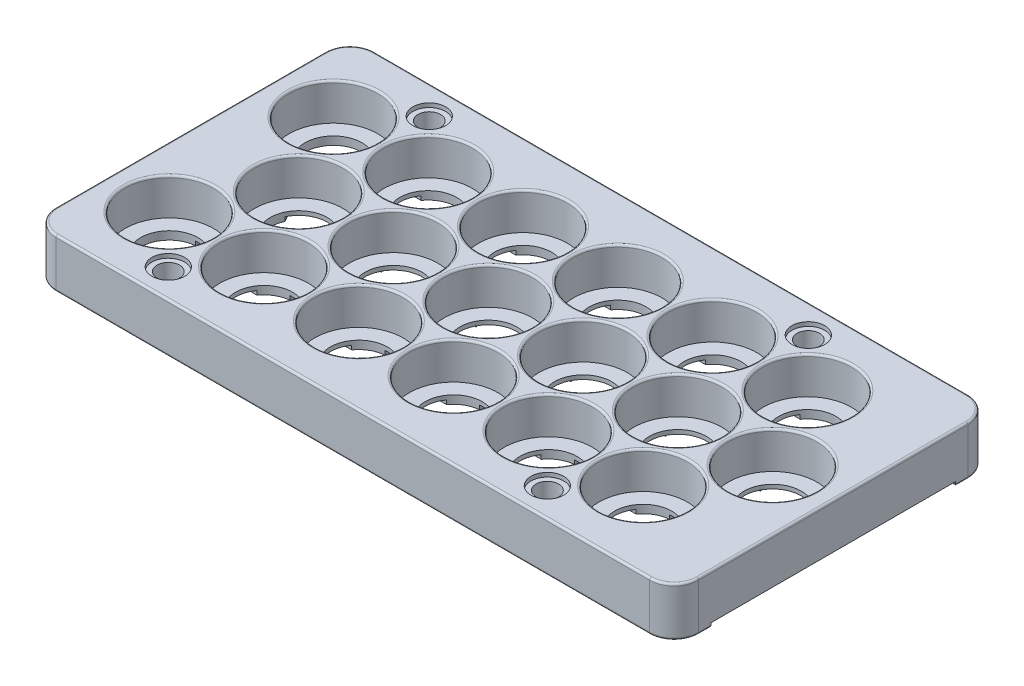
SolidWorks part; units mm, degrees
ref_plane "Front Plane" through (0, 0, 0) normal (0, 0, 1) x (1, 0, 0)
ref_plane "Top Plane" through (0, 0, 0) normal (0, 1, 0) x (1, 0, 0)
ref_plane "Right Plane" through (0, 0, 0) normal (1, 0, 0) x (0, 0, -1)
sketch "Sketch1" plane through (0, 0, 0) normal (0, 1, 0) x (1, 0, 0)
  line L0 (0, 0) -> (11.575, -20.0485) construction
  line L1 (11.575, -20.0485) -> (0, -40.097) construction
  line L2 (0, 0) -> (11.575, 0) construction
  line L3 (11.575, 0) -> (11.575, -20.0485) construction
  line L4 (11.575, -20.0485) -> (11.575, -40.097) construction
  line L5 (11.575, -40.097) -> (0, -40.097) construction
  line L6 (0, 0) -> (23.15, 0) construction
  line L7 (0, 0) -> (23.15, 0) construction
  line L8 (-14.825, -58.922) -> (142.15, -58.922)
  line L9 (-14.825, -58.922) -> (-14.825, 18.825)
  line L10 (-14.825, 18.825) -> (142.15, 18.825)
  line L11 (142.15, -58.922) -> (142.15, 18.825)
  circle A0 centre (0, 0) radius 10.825
  circle A1 centre (11.575, -20.0485) radius 10.825
  circle A2 centre (0, -40.097) radius 10.825
  circle A3 centre (23.15, 0) radius 10.825
  circle A4 centre (34.725, -20.0485) radius 10.825
  circle A5 centre (23.15, -40.097) radius 10.825
  circle A6 centre (46.3, 0) radius 10.825
  circle A7 centre (57.875, -20.0485) radius 10.825
  circle A8 centre (46.3, -40.097) radius 10.825
  circle A9 centre (69.45, 0) radius 10.825
  circle A10 centre (81.025, -20.0485) radius 10.825
  circle A11 centre (69.45, -40.097) radius 10.825
  circle A12 centre (92.6, 0) radius 10.825
  circle A13 centre (104.175, -20.0485) radius 10.825
  circle A14 centre (92.6, -40.097) radius 10.825
  circle A15 centre (115.75, 0) radius 10.825
  circle A16 centre (127.325, -20.0485) radius 10.825
  circle A17 centre (115.75, -40.097) radius 10.825
  circle A18 centre (0, 0) radius 7
  circle A19 centre (11.575, -20.0485) radius 7
  circle A20 centre (0, -40.097) radius 7
  circle A21 centre (23.15, 0) radius 7
  circle A22 centre (34.725, -20.0485) radius 7
  circle A23 centre (23.15, -40.097) radius 7
  circle A24 centre (46.3, 0) radius 7
  circle A25 centre (57.875, -20.0485) radius 7
  circle A26 centre (46.3, -40.097) radius 7
  circle A27 centre (69.45, 0) radius 7
  circle A28 centre (81.025, -20.0485) radius 7
  circle A29 centre (69.45, -40.097) radius 7
  circle A30 centre (92.6, 0) radius 7
  circle A31 centre (104.175, -20.0485) radius 7
  circle A32 centre (92.6, -40.097) radius 7
  circle A33 centre (115.75, 0) radius 7
  circle A34 centre (127.325, -20.0485) radius 7
  circle A35 centre (115.75, -40.097) radius 7
  dimension "D3" = 21.65
  dimension "D11" = 14
  dimension "D1" = 60
  dimension "D2" = 60
  dimension "D4" = 1.5
  dimension "D6" = 23.15
  dimension "D7" = 4
  dimension "D8" = 4
  dimension "D9" = 8
  dimension "D10" = 8
  dimension "D13" = 23.15
  dimension "D12" = 6
extrude "Boss-Extrude2" add sketch "Sketch1" along normal blind 11 contours L8 L11 L10 L9 A17 A16 A15 A14 A13 A12 A11 A10 A9 A8 A7 A6 A5 A4 A3 A2 A1 A0 region at (-13.0733, 0, 20.0485)
extrude "Boss-Extrude3" add sketch "Sketch1<3>" along normal blind 2 contours A0 A18 | A3 A21 | A6 A24 | A9 A27 | A12 A30 | A15 A33 | A1 A19 | A4 A22 | A7 A25 | A10 A28 | A13 A31 | A16 A34 | A17 A35 | A14 A32 | A11 A29 | A8 A26 | A5 A23 | A2 A20 region at (-10.5188, 0, 0) region at (1.0562, 0, 20.0485) region at (-10.5188, 0, 40.097) region at (12.6312, 0, 0) region at (24.2062, 0, 20.0485) region at (12.6312, 0, 40.097) region at (35.7812, 0, 0) region at (47.3562, 0, 20.0485) region at (35.7812, 0, 40.097) region at (58.9312, 0, 0) region at (70.5062, 0, 20.0485) region at (58.9312, 0, 40.097) region at (82.0812, 0, 0) region at (93.6562, 0, 20.0485) region at (82.0812, 0, 40.097) region at (105.2312, 0, 0) region at (116.8062, 0, 20.0485) region at (105.2312, 0, 40.097)
sketch "Sketch1<3>" plane through (0, 0, 0) normal (0, 1, 0) x (1, 0, 0) same geometry as "Sketch1"
sketch "Sketch2" plane through (0, 0, 0) normal (0, -1, 0) x (1, 0, 0)
  line L0 (0, 40.097) -> (11.575, 20.0485) construction
  line L1 (3.4641, 42.097) -> (15.0391, 22.0485)
  line L2 (-3.4641, 38.097) -> (8.1109, 18.0485)
  line L3 (11.575, 20.0485) -> (0, 0) construction
  line L4 (15.0391, 18.0485) -> (3.4641, -2)
  line L5 (8.1109, 22.0485) -> (-3.4641, 2)
  line L6 (19.6859, 38.097) -> (31.2609, 18.0485)
  line L7 (26.6141, 42.097) -> (38.1891, 22.0485)
  line L8 (31.2609, 22.0485) -> (19.6859, 2)
  line L9 (38.1891, 18.0485) -> (26.6141, -2)
  line L10 (23.15, 40.097) -> (34.725, 20.0485) construction
  line L11 (34.725, 20.0485) -> (23.15, 0) construction
  line L12 (42.8359, 38.097) -> (54.4109, 18.0485)
  line L13 (49.7641, 42.097) -> (61.3391, 22.0485)
  line L14 (54.4109, 22.0485) -> (42.8359, 2)
  line L15 (61.3391, 18.0485) -> (49.7641, -2)
  line L16 (46.3, 40.097) -> (57.875, 20.0485) construction
  line L17 (57.875, 20.0485) -> (46.3, 0) construction
  line L18 (65.9859, 38.097) -> (77.5609, 18.0485)
  line L19 (72.9141, 42.097) -> (84.4891, 22.0485)
  line L20 (77.5609, 22.0485) -> (65.9859, 2)
  line L21 (84.4891, 18.0485) -> (72.9141, -2)
  line L22 (69.45, 40.097) -> (81.025, 20.0485) construction
  line L23 (81.025, 20.0485) -> (69.45, 0) construction
  line L24 (89.1359, 38.097) -> (100.7109, 18.0485)
  line L25 (96.0641, 42.097) -> (107.6391, 22.0485)
  line L26 (100.7109, 22.0485) -> (89.1359, 2)
  line L27 (107.6391, 18.0485) -> (96.0641, -2)
  line L28 (92.6, 40.097) -> (104.175, 20.0485) construction
  line L29 (104.175, 20.0485) -> (92.6, 0) construction
  line L30 (112.2859, 38.097) -> (123.8609, 18.0485)
  line L31 (119.2141, 42.097) -> (130.7891, 22.0485)
  line L32 (123.8609, 22.0485) -> (112.2859, 2)
  line L33 (130.7891, 18.0485) -> (119.2141, -2)
  line L34 (115.75, 40.097) -> (127.325, 20.0485) construction
  line L35 (127.325, 20.0485) -> (115.75, 0) construction
  line L36 (-3.4641, 38.097) -> (19.6859, 38.097) construction
  line L37 (0, 40.097) -> (115.75, 40.097) construction
  line L38 (0, 44.097) -> (115.75, 44.097)
  line L39 (0, 36.097) -> (115.75, 36.097)
  line L40 (11.575, 20.0485) -> (127.325, 20.0485) construction
  line L41 (11.575, 24.0485) -> (127.325, 24.0485)
  line L42 (11.575, 16.0485) -> (127.325, 16.0485)
  line L43 (0, 0) -> (115.75, 0) construction
  line L44 (0, 4) -> (115.75, 4)
  line L45 (0, -4) -> (115.75, -4)
  arc A0 (3.4641, 42.097) -> (-3.4641, 38.097) centre (0, 40.097) ccw
  arc A1 (8.1109, 18.0485) -> (15.0391, 22.0485) centre (11.575, 20.0485) ccw
  arc A2 (15.0391, 18.0485) -> (8.1109, 22.0485) centre (11.575, 20.0485) ccw
  arc A3 (-3.4641, 2) -> (3.4641, -2) centre (0, 0) ccw
  arc A4 (26.6141, 42.097) -> (19.6859, 38.097) centre (23.15, 40.097) ccw
  arc A5 (31.2609, 18.0485) -> (38.1891, 22.0485) centre (34.725, 20.0485) ccw
  arc A6 (38.1891, 18.0485) -> (31.2609, 22.0485) centre (34.725, 20.0485) ccw
  arc A7 (19.6859, 2) -> (26.6141, -2) centre (23.15, 0) ccw
  arc A8 (49.7641, 42.097) -> (42.8359, 38.097) centre (46.3, 40.097) ccw
  arc A9 (54.4109, 18.0485) -> (61.3391, 22.0485) centre (57.875, 20.0485) ccw
  arc A10 (61.3391, 18.0485) -> (54.4109, 22.0485) centre (57.875, 20.0485) ccw
  arc A11 (42.8359, 2) -> (49.7641, -2) centre (46.3, 0) ccw
  arc A12 (72.9141, 42.097) -> (65.9859, 38.097) centre (69.45, 40.097) ccw
  arc A13 (77.5609, 18.0485) -> (84.4891, 22.0485) centre (81.025, 20.0485) ccw
  arc A14 (84.4891, 18.0485) -> (77.5609, 22.0485) centre (81.025, 20.0485) ccw
  arc A15 (65.9859, 2) -> (72.9141, -2) centre (69.45, 0) ccw
  arc A16 (96.0641, 42.097) -> (89.1359, 38.097) centre (92.6, 40.097) ccw
  arc A17 (100.7109, 18.0485) -> (107.6391, 22.0485) centre (104.175, 20.0485) ccw
  arc A18 (107.6391, 18.0485) -> (100.7109, 22.0485) centre (104.175, 20.0485) ccw
  arc A19 (89.1359, 2) -> (96.0641, -2) centre (92.6, 0) ccw
  arc A20 (119.2141, 42.097) -> (112.2859, 38.097) centre (115.75, 40.097) ccw
  arc A21 (123.8609, 18.0485) -> (130.7891, 22.0485) centre (127.325, 20.0485) ccw
  arc A22 (130.7891, 18.0485) -> (123.8609, 22.0485) centre (127.325, 20.0485) ccw
  arc A23 (112.2859, 2) -> (119.2141, -2) centre (115.75, 0) ccw
  arc A24 (0, 44.097) -> (0, 36.097) centre (0, 40.097) ccw
  arc A25 (115.75, 36.097) -> (115.75, 44.097) centre (115.75, 40.097) ccw
  arc A26 (11.575, 24.0485) -> (11.575, 16.0485) centre (11.575, 20.0485) ccw
  arc A27 (127.325, 16.0485) -> (127.325, 24.0485) centre (127.325, 20.0485) ccw
  arc A28 (0, 4) -> (0, -4) centre (0, 0) ccw
  arc A29 (115.75, -4) -> (115.75, 4) centre (115.75, 0) ccw
  point P3 (5.7875, 30.0727)
  point P8 (5.7875, 10.0242)
  point P18 (28.9375, 30.0727)
  point P25 (28.9375, 10.0242)
  point P34 (52.0875, 30.0727)
  point P39 (52.0875, 10.0242)
  point P48 (75.2375, 30.0727)
  point P53 (75.2375, 10.0242)
  point P62 (98.3875, 30.0727)
  point P67 (98.3875, 10.0242)
  point P76 (121.5375, 30.0727)
  point P81 (121.5375, 10.0242)
  point P91 (57.875, 40.097)
  point P96 (69.45, 20.0485)
  point P103 (57.875, 0)
  circle M62 centre (0, 0) radius 7
  circle M63 centre (23.15, 0) radius 7
  circle M64 centre (46.3, 0) radius 7
  circle M65 centre (69.45, 0) radius 7
  circle M66 centre (92.6, 0) radius 7
  circle M67 centre (115.75, 0) radius 7
  circle M68 centre (11.575, 20.0485) radius 7
  circle M69 centre (34.725, 20.0485) radius 7
  circle M70 centre (57.875, 20.0485) radius 7
  circle M71 centre (81.025, 20.0485) radius 7
  circle M72 centre (104.175, 20.0485) radius 7
  circle M73 centre (127.325, 20.0485) radius 7
  circle M74 centre (115.75, 40.097) radius 7
  circle M75 centre (92.6, 40.097) radius 7
  circle M76 centre (69.45, 40.097) radius 7
  circle M77 centre (46.3, 40.097) radius 7
  circle M78 centre (23.15, 40.097) radius 7
  circle M79 centre (0, 40.097) radius 7
  dimension "D1" = 8
  dimension "D3" = 23.15
  dimension "D4" = 8
  dimension "D5" = 8
  dimension "D6" = 8
extrude "Cut-Extrude1" cut sketch "Sketch2" against normal blind 1 contours L1 L39 L38 M78 M79 | L7 L39 L38 M77 M78 | L39 L2 L1 M79 M68 | L42 L8 L6 L41 M68 M69 | L6 L41 L7 L39 M69 M78 | L12 L41 L13 L39 M70 M77 | L13 L39 L38 M76 M77 | L18 L41 L19 L39 M71 M76 | L19 L39 L38 M75 M76 | L24 L41 L25 L39 M72 M75 | L25 L39 L38 M74 M75 | L30 L41 L31 M73 M74 | L42 L32 L30 L41 M72 M73 | L42 L26 L24 L41 M71 M72 | L42 L20 L18 L41 M70 M71 | L42 L14 L12 L41 M69 M70 | L45 L44 L4 M62 M63 | L44 L4 L5 M62 M68 | L45 L44 L9 M63 M64 | L45 L44 L15 M64 M65 | L45 L44 L21 M65 M66 | L45 L44 L27 M66 M67 | L44 L27 L42 L26 M66 M72 | L42 L32 L33 M67 M73 | L44 L21 L42 L20 M65 M71 | L44 L15 L42 L14 M64 M70 | L39 L13 M77 | L39 L25 M75 | L39 L19 M76 | L41 L6 M69 | L44 L4 M62 | L44 L15 M64 | L44 L21 M65 | L44 L27 M66 | L41 L30 M73 | L32 L42 M73 | L41 L24 M72 | L26 L42 M72 | L41 L18 M71 | L20 L42 M71 | L41 L12 M70 | L14 L42 M70 | L44 L9 L42 L8 M63 M69 | L8 L42 M69 | L39 L7 M78 | L39 L1 M79 | L44 A29 L45 A28 region at (11.6138, 0, 40.1242) region at (6.3461, 0, 36.4331) region at (5.7834, 0, 30.0255) region at (23.0718, 0, 20.0485) region at (28.9375, 0, 30.0727) region at (34.7638, 0, 40.1242) region at (28.3789, 0, 23.7124) region at (5.7834, 0, 10.0715) region at (29.4961, 0, 36.4331) region at (57.9138, 0, 40.1242) region at (28.3789, 0, 16.3846) region at (28.9375, 0, 10.0242) region at (6.3461, 0, 3.6639) region at (11.6138, 0, -0.0272) region at (52.0875, 0, 30.0727) region at (46.2218, 0, 20.0485) region at (52.6461, 0, 36.4331) region at (81.0638, 0, 40.1242) region at (51.5289, 0, 23.7124) region at (34.7638, 0, -0.0272) region at (75.2375, 0, 30.0727) region at (75.7961, 0, 36.4331) region at (104.2138, 0, 40.1242) region at (74.6789, 0, 23.7124) region at (69.3718, 0, 20.0485) region at (51.5289, 0, 16.3846) region at (52.0875, 0, 10.0242) region at (57.9138, 0, -0.0272) region at (98.3875, 0, 30.0727) region at (98.9461, 0, 36.4331) region at (97.8289, 0, 23.7124) region at (92.5218, 0, 20.0485) region at (74.6789, 0, 16.3846) region at (52.6461, 0, 3.6639) region at (81.0638, 0, -0.0272) region at (121.5416, 0, 30.12) region at (75.2375, 0, 10.0242) region at (120.9789, 0, 23.7124) region at (115.6718, 0, 20.0485) region at (97.8289, 0, 16.3846) region at (75.7961, 0, 3.6639) region at (104.2138, 0, -0.0272) region at (98.3875, 0, 10.0242) region at (121.5416, 0, 9.977) region at (120.9789, 0, 16.3846) region at (98.9461, 0, 3.6639)
sketch "Sketch9" plane through (0, 11, 0) normal (0, 1, 0) x (1, 0, 0)
  line L0 (11.575, -58.922) -> (11.575, 18.825)
  line L1 (-14.825, 18.825) -> (142.15, 18.825) construction
  line L2 (104.175, 18.825) -> (104.175, -58.922)
  line L3 (-14.825, -58.922) -> (142.15, -58.922) construction
  circle A0 centre (11.575, 11.825) radius 2.75
  circle A1 centre (11.575, -51.922) radius 2.75
  circle A2 centre (104.175, -51.922) radius 2.75
  circle A3 centre (104.175, 11.825) radius 2.75
  point P0 (11.575, 11.825)
  point P7 (11.575, -20.0485)
  point P15 (104.175, -20.0485)
  point P20 (104.175, 11.825)
  point P21 (104.175, -51.922)
  point P22 (11.575, -51.922)
  dimension "D5" = 5.5
  dimension "D1" = 7
  dimension "D4" = 7
extrude "Cut-Extrude3" cut sketch "Sketch9" against normal up to next contours A2 | A1 | A0 | A3
sketch "Sketch12" plane through (0, 11, 0) normal (0, 1, 0) x (1, 0, 0)
  circle A0 centre (11.575, 11.825) radius 4
  circle A1 centre (104.175, 11.825) radius 4
  circle A2 centre (11.575, -51.922) radius 4
  circle A3 centre (104.175, -51.922) radius 4
  dimension "D1" = 8
extrude "Cut-Extrude4" cut sketch "Sketch12" against normal blind 1
sketch "Sketch11" plane through (0, 0, 0) normal (0, -1, 0) x (1, 0, 0)
  line L0 (142.15, 58.922) -> (142.15, -18.825) construction
  line L1 (-14.825, 58.922) -> (142.15, 58.922)
  line L2 (-14.825, 58.922) -> (-14.825, 49.922)
  line L3 (-14.825, 49.922) -> (142.15, 49.922)
  line L4 (142.15, 58.922) -> (142.15, 49.922)
  line L5 (11.575, 20.0485) -> (104.175, 20.0485) construction
  line L6 (142.15, -18.825) -> (142.15, -9.825)
  line L7 (-14.825, -9.825) -> (142.15, -9.825)
  line L8 (-14.825, -18.825) -> (-14.825, -9.825)
  line L9 (-14.825, -18.825) -> (142.15, -18.825)
  circle A0 centre (11.575, 51.922) radius 6
  circle A1 centre (104.175, 51.922) radius 6
  circle A2 centre (11.575, 51.922) radius 6.875
  circle A3 centre (104.175, 51.922) radius 6.875
  circle A4 centre (104.175, -11.825) radius 6.875
  circle A5 centre (11.575, -11.825) radius 6.875
  circle A6 centre (104.175, -11.825) radius 6
  circle A7 centre (11.575, -11.825) radius 6
  line M9 (142.15, 58.922) -> (-14.825, 58.922)
  line M10 (-14.825, 58.922) -> (-14.825, -18.825)
  line M11 (-14.825, -18.825) -> (142.15, -18.825)
  line M12 (142.15, -18.825) -> (142.15, 58.922)
  dimension "D2" = 12
  dimension "D3" = 13.75
  dimension "D1" = 9
extrude "Boss-Extrude5" add sketch "Sketch11" along normal blind 1 contours A3 L3 A2 M12 M9 M10 | L7 A5 A4 M10 M11 M12 | L3 A2 A0 | L3 A2 A0 | L3 A3 A1 | L3 A3 A1 | L7 A6 A4 | L7 A6 A4 | L7 A7 A5 | L7 A7 A5 region at (64.632, 0, 54.5272) region at (10.5881, 0, 58.5604) region at (5.4577, 0, 49.7817) region at (64.632, 0, -14.4302) region at (104.175, 0, 45.1873) region at (110.2923, 0, 50.0856) region at (11.575, 0, -5.0903) region at (5.4577, 0, -9.9887) region at (110.8134, 0, -10.8381) region at (110.2923, 0, -9.6847)
fillet "Fillet2" radius 6 4 edges at (142.15, 5, 58.922) (142.15, 5, -18.825) (-14.825, 5, -18.825) (-14.825, 5, 58.922)
fillet "Fillet4" radius 0.5 26 edges at (-13.0676, 11, 57.1646) (-14.825, 11, 20.0485) (-13.0676, 11, -17.0676) (63.6625, 11, -18.825) (140.3926, 11, -17.0676) (142.15, 11, 20.0485) (140.3926, 11, 57.1646) (63.6625, 11, 58.922) (0, 11, 10.825) (11.575, 11, 30.8735) (0, 11, 50.922) (23.15, 11, 10.825) (34.725, 11, 30.8735) (23.15, 11, 50.922) (46.3, 11, 10.825) (57.875, 11, 30.8735) (46.3, 11, 50.922) (69.45, 11, 10.825) (81.025, 11, 30.8735) (69.45, 11, 50.922) (92.6, 11, 10.825) (104.175, 11, 30.8735) (92.6, 11, 50.922) (115.75, 11, 10.825) (127.325, 11, 30.8735) (115.75, 11, 50.922)
fillet "Fillet5" radius 0.5 24 edges at (104.175, -1, -17.825) (11.575, -1, -17.825) (-13.0676, -1, -17.0676) (-14.825, -1, -11.325) (-4.9138, -1, -9.825) (11.575, -1, -4.95) (57.875, -1, -9.825) (104.175, -1, -4.95) (126.4513, -1, -9.825) (142.15, -1, -11.325) (140.3926, -1, -17.0676) (63.6625, -1, -18.825) (11.575, -1, 45.922) (104.175, -1, 45.922) (126.4513, -1, 49.922) (104.175, -1, 45.047) (57.875, -1, 49.922) (11.575, -1, 45.047) (-4.9138, -1, 49.922) (-14.825, -1, 51.422) (-13.0676, -1, 57.1646) (63.6625, -1, 58.922) (140.3926, -1, 57.1646) (142.15, -1, 51.422)
equation "\"hole_diameter\"= 21.65"
equation "\"D3@Sketch1\"=\"hole_diameter\""
equation "\"cell_spacing\"= 1.5"
equation "\"D4@Sketch1\"=\"cell_spacing\""
equation "\"D6@Sketch1\"=\"hole_diameter\"+\"cell_spacing\""
equation "\"len_spacing\"= 4"
equation "\"D7@Sketch1\"=\"len_spacing\""
equation "\"D8@Sketch1\"=\"len_spacing\""
equation "\"wid_spacing\"= 8"
equation "\"D9@Sketch1\"=\"wid_spacing\""
equation "\"D10@Sketch1\"=\"wid_spacing\""
equation "\"nipple\"= 14"
equation "\"D11@Sketch1\"=\"nipple\""
equation "\"D13@Sketch1\"=\"hole_diameter\"+\"cell_spacing\""
equation "\"channel\"= 8"
equation "\"D1@Sketch2\"=\"channel\""
equation "\"D3@Sketch2\"=\"hole_diameter\"+\"cell_spacing\""
equation "\"D4@Sketch2\"=\"channel\""
equation "\"D5@Sketch2\"=\"channel\""
equation "\"D6@Sketch2\"=\"channel\""
equation "\"lip\"= 9"
equation "\"lip_height\"= 1"
equation "\"outer_fillet\"=6"
equation "\"D1@Fillet2\"=\"outer_fillet\""
equation "\"heat_insert\"=5.5"
equation "\"D5@Sketch9\"=\"heat_insert\""
equation "\"insert_placement\"= 7"
equation "\"D4@Sketch9\"=\"insert_placement\""
equation "\"D1@Sketch9\"=\"insert_placement\""
equation "\"heat_insert_lip\"=12"
equation "\"D1@Sketch11\"=\"lip\""
equation "\"D2@Sketch11\"=\"heat_insert_lip\""
equation "\"D3@Sketch11\"= \"heat_insert_lip\" + 1.75"
